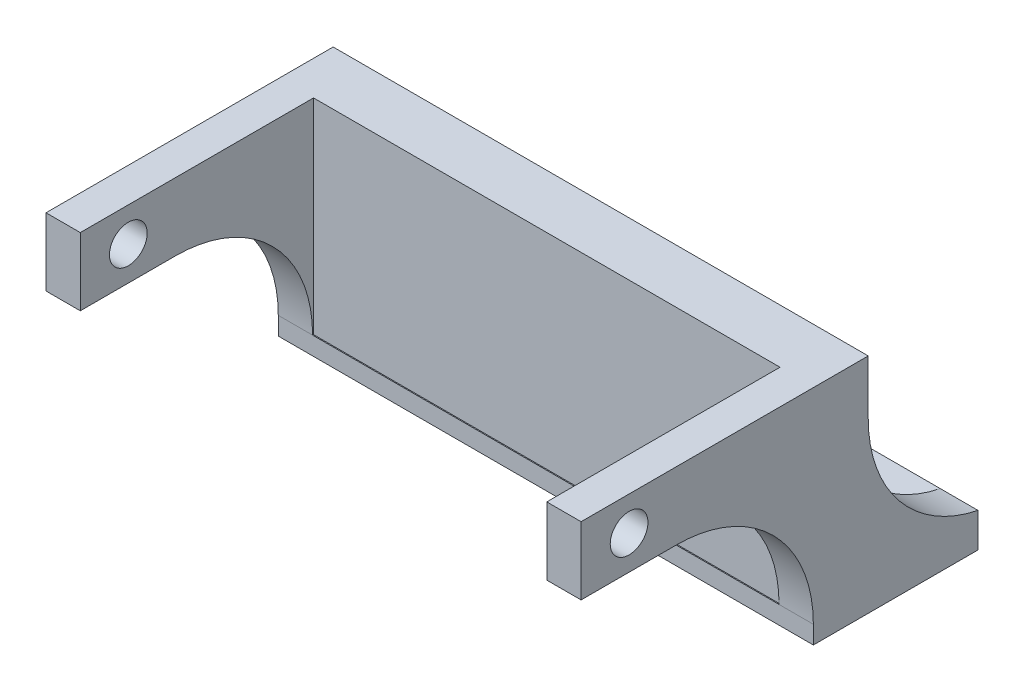
SolidWorks part; units mm, degrees
ref_plane "Front Plane" through (0, 0, 0) normal (0, 0, 1) x (1, 0, 0)
ref_plane "Top Plane" through (0, 0, 0) normal (0, 1, 0) x (1, 0, 0)
ref_plane "Right Plane" through (0, 0, 0) normal (1, 0, 0) x (0, 0, -1)
sketch "Sketch1" plane through (0, 0, 0) normal (0, 1, 0) x (1, 0, 0)
  line L1 (-39, 12) -> (39, 12)
  line L2 (-39, 12) -> (-39, -12)
  line L3 (-39, -12) -> (39, -12)
  line L4 (39, 12) -> (39, -12)
  line L5 (-39, 12) -> (39, -12) construction
  line L6 (-39, -12) -> (39, 12) construction
  point P0 (0, 0)
  dimension "D1" = 24
  dimension "D2" = 78
extrude "Boss-Extrude1" add sketch "Sketch1" along normal blind 5 contours L4 L3 L2 L1
sketch "Sketch2" plane through (0, 5, 0) normal (0, 1, 0) x (1, 0, 0)
  line L0 (39, 12) -> (39, -12) construction
  line L1 (-39, -12) -> (39, -12)
  line L2 (-39, -12) -> (-39, -4)
  line L4 (39, -12) -> (39, -4)
  line L6 (39, -4) -> (-39, -4)
  dimension "D1" = 8
extrude "Boss-Extrude2" add sketch "Sketch2" along normal blind 27.5
fillet "Fillet1" radius 20 1 edges
sketch "Sketch3" plane through (0, 0, -12) normal (0, 0, -1) x (-1, 0, 0)
  line L0 (39, 5) -> (-39, 5) construction
  line L1 (-33.5, 5) -> (33.5, 5)
  line L2 (-33.5, 5) -> (-33.5, 24.5959)
  line L3 (-33.5, 24.5959) -> (33.5, 24.5959)
  line L4 (33.5, 5) -> (33.5, 24.5959)
  line L5 (-39, 24.5959) -> (39, 24.5959) construction
  line L6 (0, 24.5959) -> (0, 0) construction
  line L7 (39, 0) -> (-39, 0) construction
  line L8 (-39, 5) -> (-39, 0) construction
  dimension "D1" = 5.5
extrude "Cut-Extrude1" cut sketch "Sketch3" against normal blind 16
sketch "Sketch4" plane through (-39, 0, 0) normal (-1, 0, 0) x (0, 0, 1)
  line L0 (12, 27.56) -> (38.86, 27.56) construction
  line L1 (12, 32.5) -> (12, 0) construction
  line L2 (4, 32.5) -> (12, 32.5) construction
  line L3 (12, 32.5) -> (45.86, 32.5)
  line L4 (12, 32.5) -> (12, 22.62)
  line L5 (12, 22.62) -> (45.86, 22.62)
  line L6 (45.86, 32.5) -> (45.86, 22.62)
  line L7 (45.86, 27.56) -> (38.86, 27.56) construction
  line L8 (-12, 0) -> (12, 0) construction
  circle A0 centre (38.86, 27.56) radius 2.75
  dimension "D1" = 5.5
  dimension "D2" = 27.56
  dimension "D3" = 26.86
  dimension "D4" = 7
extrude "Boss-Extrude3" add sketch "Sketch4" against normal blind 78
fillet "Fillet2" radius 20 1 edges
sketch "Sketch5" plane through (0, 0, 45.86) normal (0, 0, 1) x (1, 0, 0)
  line L1 (34, 22.62) -> (-34, 22.62)
  line L2 (34, 22.62) -> (34, 2.62)
  line L3 (34, 2.62) -> (-34, 2.62)
  line L4 (-34, 22.62) -> (-34, 2.62)
  line L5 (0, 2.62) -> (0, 32.5) construction
  line L6 (39, 32.5) -> (-39, 32.5) construction
  line L7 (39, 22.62) -> (39, 32.5) construction
  line L8 (39, 2.62) -> (-39, 2.62) construction
  line L9 (39, 22.62) -> (-39, 22.62) construction
  dimension "D1" = 5
extrude "Cut-Extrude2" cut sketch "Sketch5" against normal blind 34
sketch "Sketch6" plane through (0, 0, 45.86) normal (0, 0, 1) x (1, 0, 0)
  line L0 (39, 22.62) -> (-39, 22.62) construction
  line L1 (34, 22.62) -> (-34, 22.62)
  line L2 (34, 22.62) -> (34, 32.5)
  line L3 (34, 32.5) -> (-34, 32.5)
  line L4 (-34, 22.62) -> (-34, 32.5)
  line L5 (39, 32.5) -> (-39, 32.5) construction
  line L6 (34, 22.62) -> (34, 2.62) construction
  line L7 (-34, 2.62) -> (-34, 22.62) construction
extrude "Cut-Extrude3" cut sketch "Sketch6" against normal blind 34
